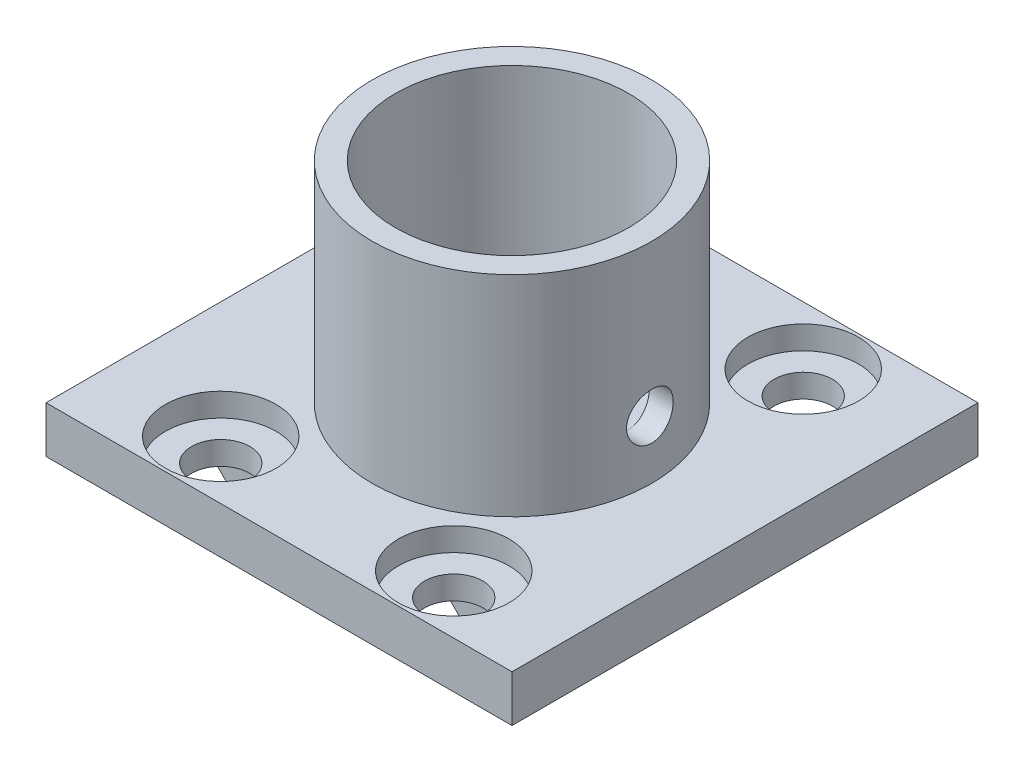
SolidWorks part; units mm, degrees
ref_plane "Front Plane" through (0, 0, 0) normal (0, 0, 1) x (1, 0, 0)
ref_plane "Top Plane" through (0, 0, 0) normal (0, 1, 0) x (1, 0, 0)
ref_plane "Right Plane" through (0, 0, 0) normal (1, 0, 0) x (0, 0, -1)
sketch "Sketch1" plane through (0, 0, 0) normal (0, 0, 1) x (1, 0, 0)
  line L0 (-15.8729, 29.999) -> (-14.0729, 28.199)
  line L1 (-21.2929, 51.999) -> (18.7071, 51.999)
  line L2 (-21.2929, 51.999) -> (-21.2929, 29.999)
  line L3 (-21.2929, 29.999) -> (-15.8729, 29.999)
  line L4 (18.7071, 51.999) -> (18.7071, 29.999)
  line L5 (-14.0729, 28.199) -> (-16.7929, 28.199)
  line L6 (-16.7929, 28.199) -> (-16.7929, 26.559)
  line L7 (-16.7929, 26.559) -> (-14.1329, 23.899)
  line L8 (-14.1329, 23.899) -> (-8.4529, 23.899)
  line L9 (-11.2929, 23.899) -> (-11.2929, 29.999) construction
  line L10 (-5.7929, 26.559) -> (-8.4529, 23.899)
  line L11 (-5.7929, 28.199) -> (-5.7929, 26.559)
  line L12 (-8.5129, 28.199) -> (-5.7929, 28.199)
  line L13 (-6.7129, 29.999) -> (-8.5129, 28.199)
  line L14 (-1.2929, 11.999) -> (-1.2929, 0.7497) construction
  line L15 (8.7071, 23.899) -> (8.7071, 29.999) construction
  line L16 (4.1271, 29.999) -> (5.9271, 28.199)
  line L17 (5.9271, 28.199) -> (3.2071, 28.199)
  line L18 (3.2071, 28.199) -> (3.2071, 26.559)
  line L19 (3.2071, 26.559) -> (5.8671, 23.899)
  line L20 (11.5471, 23.899) -> (5.8671, 23.899)
  line L21 (14.2071, 26.559) -> (11.5471, 23.899)
  line L22 (14.2071, 28.199) -> (14.2071, 26.559)
  line L23 (11.4871, 28.199) -> (14.2071, 28.199)
  line L24 (13.2871, 29.999) -> (11.4871, 28.199)
  line L25 (-6.7129, 29.999) -> (4.1271, 29.999)
  line L26 (13.2871, 29.999) -> (18.7071, 29.999)
  dimension "D1" = 40
  dimension "D2" = 22
  dimension "D3" = 45
  dimension "D4" = 5.42
  dimension "D5" = 1.8
  dimension "D6" = 4.3
  dimension "D7" = 4.5
  dimension "D8" = 1.64
  dimension "D9" = 10
extrude "Boss-Extrude1" add sketch "Sketch1" along normal blind 40
other "Move Face1" flip direction yes face at (12.8471, 28.199, 20) face at (12.3871, 29.099, 20) face at (14.2071, 27.379, 20) face at (12.8771, 25.229, 20) face at (8.7071, 23.899, 20) face at (3.2071, 27.379, 20) face at (4.5671, 28.199, 20) face at (4.5371, 25.229, 20) face at (5.0271, 29.099, 20) face at (-7.6129, 29.099, 20) face at (-7.1529, 28.199, 20) face at (-5.7929, 27.379, 20) face at (-7.1229, 25.229, 20) face at (-11.2929, 23.899, 20) face at (-15.4629, 25.229, 20) face at (-16.7929, 27.379, 20) face at (-15.4329, 28.199, 20) face at (-14.9729, 29.099, 20) offset 0.2 parameters "D1"=0.2
sketch "Sketch2" plane through (0, 29.999, 0) normal (0, -1, 0) x (1, 0, 0)
  line L1 (-21.2929, 30) -> (18.7071, 30)
  line L2 (-21.2929, 30) -> (-21.2929, 10)
  line L3 (-21.2929, 10) -> (18.7071, 10)
  line L4 (18.7071, 30) -> (18.7071, 10)
  line L5 (-21.2929, 40) -> (-21.2929, 0) construction
  line L6 (18.7071, 40) -> (18.7071, 0) construction
  line L7 (-6.9958, 0) -> (4.4099, 0) construction
  dimension "D1" = 20
  dimension "D2" = 10
extrude "Cut-Extrude1" cut sketch "Sketch2" along normal through all flip side to cut
sketch "Sketch3" plane through (0, 51.999, 0) normal (0, 1, 0) x (1, 0, 0)
  line L0 (18.7071, 0) -> (-21.2929, 0) construction
  line L1 (-21.2929, -40) -> (-21.2929, 0) construction
  circle A0 centre (-1.2929, -20) radius 10
  point P4 (0, 0)
  point P5 (-1.2929, 0)
  point P6 (0, 0)
  point P9 (-21.2929, -20)
  dimension "D1" = 20
extrude "Cut-Extrude2" cut sketch "Sketch3" against normal blind 15
sketch "Sketch4" plane through (18.7071, 0, 0) normal (1, 0, 0) x (0, 0, -1)
  line L0 (-40, 51.999) -> (0, 51.999) construction
  circle A0 centre (-20, 38.999) radius 2
  point P4 (-20, 51.999)
  dimension "D1" = 4
  dimension "D2" = 13
extrude "Cut-Extrude3" cut sketch "Sketch4" against normal up to body separate body
sketch "Sketch5" plane through (0, 29.999, 0) normal (0, -1, 0) x (1, 0, 0)
  circle A0 centre (-1.2929, 20) radius 2
  circle A1 centre (-1.2929, 20) radius 10 construction
  dimension "D1" = 4
extrude "Cut-Extrude4" cut sketch "Sketch5" against normal through all
sketch "Sketch6" plane through (0, 29.999, 0) normal (0, -1, 0) x (1, 0, 0)
  circle A0 centre (-1.2929, 20) radius 4
  dimension "D1" = 8
extrude "Cut-Extrude5" cut sketch "Sketch6" against normal blind 4
sketch "Sketch7" plane through (0, 51.999, 0) normal (0, 1, 0) x (1, 0, 0)
  circle A0 centre (-1.2929, -20) radius 12
  dimension "D1" = 24
extrude "Cut-Extrude6" cut sketch "Sketch7" against normal blind 18 flip side to cut
sketch "Sketch8" plane through (0, 33.999, 0) normal (0, 1, 0) x (1, 0, 0)
  line L0 (18.7071, -40) -> (18.7071, 0) construction
  line L1 (18.7071, 0) -> (-21.2929, 0) construction
  line L2 (18.7071, -20) -> (-21.2929, -20) construction
  line L3 (-21.2929, 0) -> (-21.2929, -40) construction
  line L4 (-1.2929, 0) -> (-1.2929, -40) construction
  line L5 (18.7071, -40) -> (-21.2929, -40) construction
  circle A0 centre (8.7071, -5) radius 2.5
  circle A1 centre (-11.2929, -5) radius 2.5
  circle A2 centre (-11.2929, -35) radius 2.5
  circle A3 centre (8.7071, -35) radius 2.5
  dimension "D1" = 5
  dimension "D2" = 10
  dimension "D3" = 5
extrude "Cut-Extrude9" cut sketch "Sketch8" against normal through all
sketch "Sketch9" plane through (0, 33.999, 0) normal (0, 1, 0) x (1, 0, 0)
  line L0 (18.7071, -20) -> (-21.2929, -20) construction
  line L1 (18.7071, -40) -> (18.7071, 0) construction
  line L2 (-21.2929, 0) -> (-21.2929, -40) construction
  line L3 (-1.2929, 0) -> (-1.2929, -40) construction
  line L4 (18.7071, 0) -> (-21.2929, 0) construction
  line L5 (18.7071, -40) -> (-21.2929, -40) construction
  circle A0 centre (8.7071, -5) radius 4.75
  circle A1 centre (8.7071, -35) radius 4.75
  circle A2 centre (-11.2929, -35) radius 4.75
  circle A3 centre (-11.2929, -5) radius 4.75
  dimension "D1" = 9.5
extrude "Cut-Extrude10" cut sketch "Sketch9" against normal offset from surface (2 mm away) 2 up to face at (8.7071, 29.999, 37.5)
